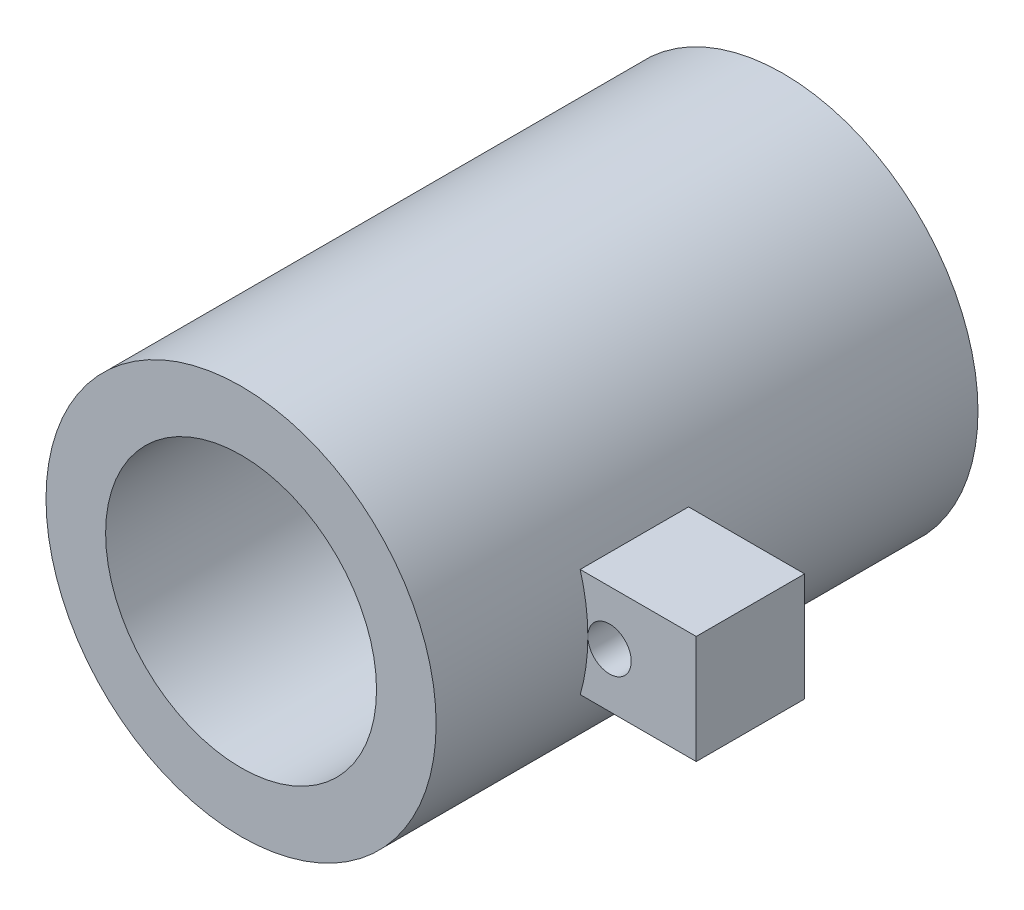
SolidWorks part; units mm, degrees
ref_plane "Ebene vorne" through (0, 0, 0) normal (0, 0, 1) x (1, 0, 0)
ref_plane "Ebene oben" through (0, 0, 0) normal (0, 1, 0) x (1, 0, 0)
ref_plane "Ebene rechts" through (0, 0, 0) normal (1, 0, 0) x (0, 0, -1)
sketch "Skizze1" plane through (0, 0, 0) normal (0, 0, 1) x (1, 0, 0)
  circle A0 centre (0, 0) radius 9
  circle A1 centre (0, 0) radius 6.25
  dimension "D1" = 18
  dimension "D2" = 12.5
extrude "Aufsatz-Linear austragen1" add sketch "Skizze1" along normal mid plane 25
sketch "Skizze2" plane through (0, 0, 0) normal (1, 0, 0) x (0, 0, -1)
  line L0 (9.9, 0) -> (-9.9, 0) construction
  line L1 (-5.5, 2.5) -> (-0.5, 2.5)
  line L2 (-5.5, 2.5) -> (-5.5, -2.5)
  line L3 (-5.5, -2.5) -> (-0.5, -2.5)
  line L4 (-0.5, 2.5) -> (-0.5, -2.5)
  line L5 (-5.5, 2.5) -> (-0.5, -2.5) construction
  line L6 (-5.5, -2.5) -> (-0.5, 2.5) construction
  line L7 (0, 9.9) -> (0, -9.9) construction
  point P0 (-3, 0)
  dimension "D1" = 5
  dimension "D2" = 5
  dimension "D3" = 3
extrude "Aufsatz-Linear austragen2" add sketch "Skizze2" along normal blind 6 from offset 8
sketch "Skizze3" plane through (0, 0, 5.5) normal (0, 0, 1) x (1, 0, 0)
  line L0 (55, 0) -> (-55, 0) construction
  line L2 (0, -55) -> (0, 55) construction
  circle A0 centre (10, 0) radius 1
  point P4 (0, 0)
  dimension "D1" = 2
  dimension "D2" = 10
extrude "Schnitt-Linear austragen1" cut sketch "Skizze3" against normal blind 8
